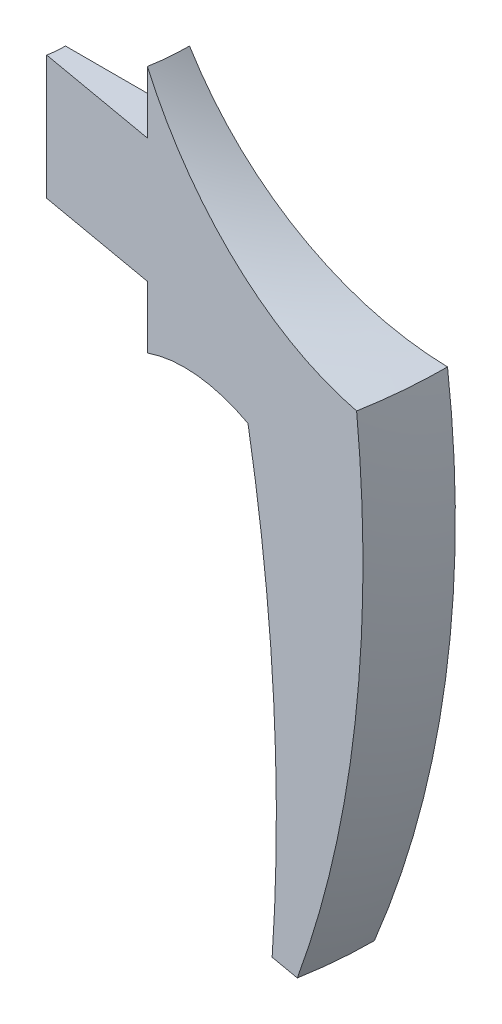
SolidWorks part; units mm, degrees
ref_plane "Front Plane" through (0, 0, 0) normal (0, 0, 1) x (1, 0, 0)
ref_plane "Top Plane" through (0, 0, 0) normal (0, 1, 0) x (1, 0, 0)
ref_plane "Right Plane" through (0, 0, 0) normal (1, 0, 0) x (0, 0, -1)
sketch "Sketch2" plane through (0, 0, 0) normal (0, 0, 1) x (1, 0, 0)
  line L0 (0, 0) -> (36, 0) construction
  line L1 (36, -20) -> (56, -18.2502) construction
  line L2 (77.5841, -4.0086) -> (65.7952, -90) construction
  line L3 (60.7952, -90) -> (65.7952, -90)
  line L4 (36, -20) -> (36, 20)
  line L5 (36, 20) -> (36, 0) construction
  line L6 (16, -10) -> (16, 10)
  line L7 (16, 10) -> (36, 10)
  line L8 (36, -10) -> (16, -10)
  line L9 (36, 20) -> (77.5841, -4.0086) construction
  line L10 (56, -18.2502) -> (60.7952, -90)
  line L11 (0, 0) -> (0, -20)
  line L14 (0, 0) -> (16, 0)
  arc A0 (36, 20) -> (77.5841, -4.0086) centre (78.7214, 45.9785) ccw
  arc A1 (77.5841, -4.0086) -> (65.7952, -90) centre (-91.1545, -24.6794) cw
  arc A2 (56, -18.2502) -> (60.7952, -90) centre (-178.3657, -69.9487) cw
  arc A3 (56, -18.2502) -> (36, -20) centre (48.464, -47.2883) ccw
  point P13 (36, 20)
  point P14 (36, 20)
  point P16 (36, 0)
  point P19 (16, 0)
  point P26 (45.8493, -17.4024)
  dimension "D5" = 240
  dimension "D6" = 85
  dimension "D7" = 90
  dimension "D8" = 170
  dimension "D10" = 20
  dimension "D11" = 30
  dimension "D14" = 50
  dimension "D2" = 20
  dimension "D3" = 40
  dimension "D4" = 20
  dimension "D9" = 5
  dimension "D12" = 85.9914
  dimension "D13" = 60
  dimension "D15" = 112.194
  dimension "D16" = 16
  dimension "D17" = 20
revolve "Revolve1" add sketch "Sketch2" angle 10 about L11 region at (61.3209, -28.3997, 0) region at (26, 0, 0)
